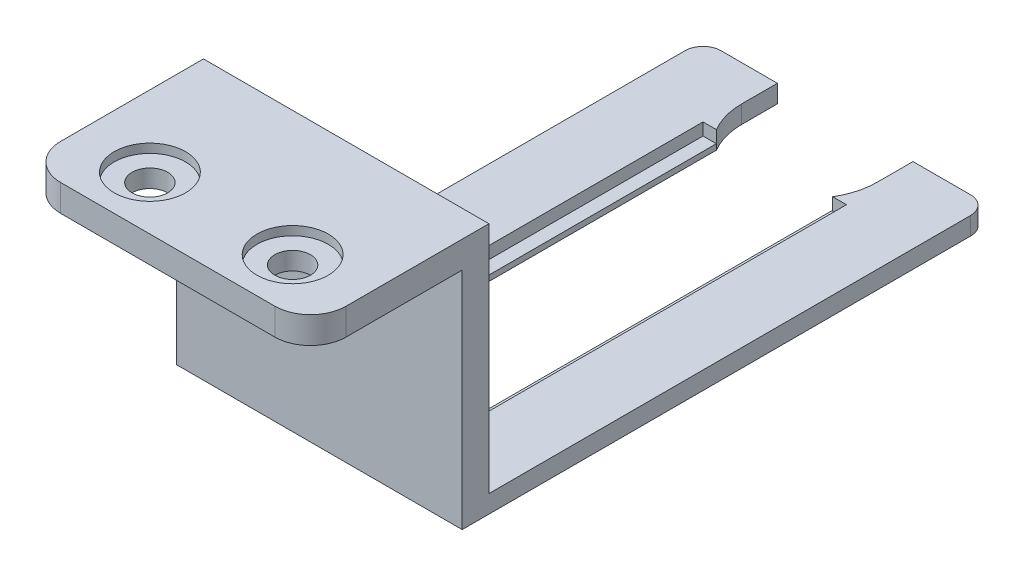
SolidWorks part; units mm, degrees
ref_plane "Front Plane" through (0, 0, 0) normal (0, 0, 1) x (1, 0, 0)
ref_plane "Top Plane" through (0, 0, 0) normal (0, 1, 0) x (1, 0, 0)
ref_plane "Right Plane" through (0, 0, 0) normal (1, 0, 0) x (0, 0, -1)
sketch "Sketch1" plane through (0, 0, 0) normal (0, 1, 0) x (1, 0, 0)
  line L0 (-12.7, 0) -> (-12.7, 22.2322)
  line L1 (-12.7, 22.2322) -> (12.7, 22.2322)
  line L2 (12.7, 22.2322) -> (12.7, 0)
  line L3 (12.7, 0) -> (12.7, -9.525)
  line L4 (12.7, -9.525) -> (-12.7, -9.525)
  line L5 (-12.7, -9.525) -> (-12.7, 0)
  circle A0 centre (0, 0) radius 3.175
  circle A1 centre (0, 0) radius 6.35
  dimension "D1" = 12.7
  dimension "D2" = 6.35
  dimension "D3" = 9.525
extrude "Boss-Extrude1" add sketch "Sketch1" along normal blind 3.175 contours A1 A0 region at (-6.1704, 0, 0)
extrude "Boss-Extrude2" add sketch "Sketch1<3>" along normal blind 4.7625 contours L5 L4 L3 L2 L1 L0 A1 region at (0, 0, -7.5373)
sketch "Sketch1<3>" plane through (0, 0, 0) normal (0, 1, 0) x (1, 0, 0) same geometry as "Sketch1"
ref_plane "Plane1" through (12.7, 0, 0) normal (1, 0, 0) x (0, 0, -1)
mirror "Mirror1" about plane through (12.7, 0, 0) normal (1, 0, 0) of bodies 102
fillet "Fillet1" radius 6.35 2 edges at (38.1, 2.3813, 9.525) (-12.7, 2.3813, 9.525)
sketch "Sketch4" plane through (0, 0, 0) normal (0, -1, 0) x (1, 0, 0)
  line L0 (38.1, 3.175) -> (38.1, -22.2322) construction
  line L1 (-12.7, -22.2322) -> (38.1, -22.2322)
  line L2 (-12.7, -22.2322) -> (-12.7, -17.4697)
  line L3 (-12.7, -17.4697) -> (38.1, -17.4697)
  line L4 (38.1, -22.2322) -> (38.1, -17.4697)
  dimension "D1" = 4.7625
extrude "Boss-Extrude3" add sketch "Sketch4" along normal blind 40
sketch "Sketch5" plane through (0, 0, -22.2322) normal (0, 0, -1) x (-1, 0, 0)
  line L0 (12.7, 4.7625) -> (12.7, -40) construction
  line L1 (-38.1, -40) -> (12.7, -40)
  line L2 (-38.1, -40) -> (-38.1, -36.825)
  line L3 (-38.1, -36.825) -> (12.7, -36.825)
  line L4 (12.7, -40) -> (12.7, -36.825)
  dimension "D1" = 3.175
extrude "Boss-Extrude4" add sketch "Sketch5" along normal blind 88.9
sketch "Sketch10" plane through (0, 0, -111.1322) normal (0, 0, -1) x (-1, 0, 0)
  line L1 (-38.1, -36.825) -> (12.7, -36.825)
  line L2 (-38.1, -36.825) -> (-38.1, -40)
  line L3 (-38.1, -40) -> (12.7, -40)
  line L4 (12.7, -36.825) -> (12.7, -40)
fillet "Fillet2" radius 3.175 2 edges at (-12.7, -38.4125, -111.1322) (38.1, -38.4125, -111.1322)
sketch "Sketch11" plane through (0, -36.825, 0) normal (0, 1, 0) x (1, 0, 0)
  line L0 (-12.7, 22.2322) -> (38.1, 22.2322) construction
  line L1 (25.4, 22.2322) -> (-0.127, 22.2322)
  line L2 (25.4, 22.2322) -> (25.4, 98.5592)
  line L3 (25.4, 98.5592) -> (-0.127, 98.5592)
  line L4 (-0.127, 22.2322) -> (-0.127, 98.5592)
  line L5 (38.1, 107.9572) -> (38.1, 22.2322) construction
  dimension "D1" = 25.527
  dimension "D2" = 76.327
  dimension "D3" = 12.7
extrude "Cut-Extrude2" cut sketch "Sketch11" against normal through all
sketch "Sketch12" plane through (0, -40, 0) normal (0, -1, 0) x (1, 0, 0)
  line L0 (25.4, -98.5592) -> (-0.127, -98.5592) construction
  line L1 (-0.127, -22.2322) -> (2.2427, -22.2322)
  line L2 (-0.127, -22.2322) -> (-0.127, -98.5592)
  line L3 (-0.127, -98.5592) -> (2.2427, -98.5592)
  line L4 (2.2427, -22.2322) -> (2.2427, -98.5592)
  line L6 (25.4, -22.2322) -> (22.8448, -22.2322)
  line L7 (25.4, -22.2322) -> (25.4, -98.5592)
  line L8 (25.4, -98.5592) -> (22.8448, -98.5592)
  line L9 (22.8448, -22.2322) -> (22.8448, -98.5592)
extrude "Boss-Extrude5" add sketch "Sketch12" against normal blind 1
sketch "Sketch14" plane through (0, -36.825, 0) normal (0, 1, 0) x (1, 0, 0)
  line L0 (-9.525, 111.1322) -> (34.925, 111.1322) construction
  line L1 (0.535, 104.7822) -> (0.535, 111.1322)
  line L2 (0.535, 111.1322) -> (24.665, 111.1322)
  line L3 (24.665, 111.1322) -> (24.665, 104.7822)
  line L4 (2.2427, 98.5592) -> (22.8448, 98.5592)
  line L5 (2.2427, 98.5592) -> (2.2427, 98.5943)
  line L9 (22.8448, 98.4098) -> (22.8448, 98.5592)
  arc A0 (0.535, 104.7822) -> (2.2427, 98.5943) centre (12.6, 104.7822) ccw
  arc A2 (22.8448, 98.4098) -> (24.665, 104.7822) centre (12.6, 104.7822) ccw
  dimension "D2" = 24.13
  dimension "D1" = 6.35
extrude "Cut-Extrude3" cut sketch "Sketch14" against normal through all
